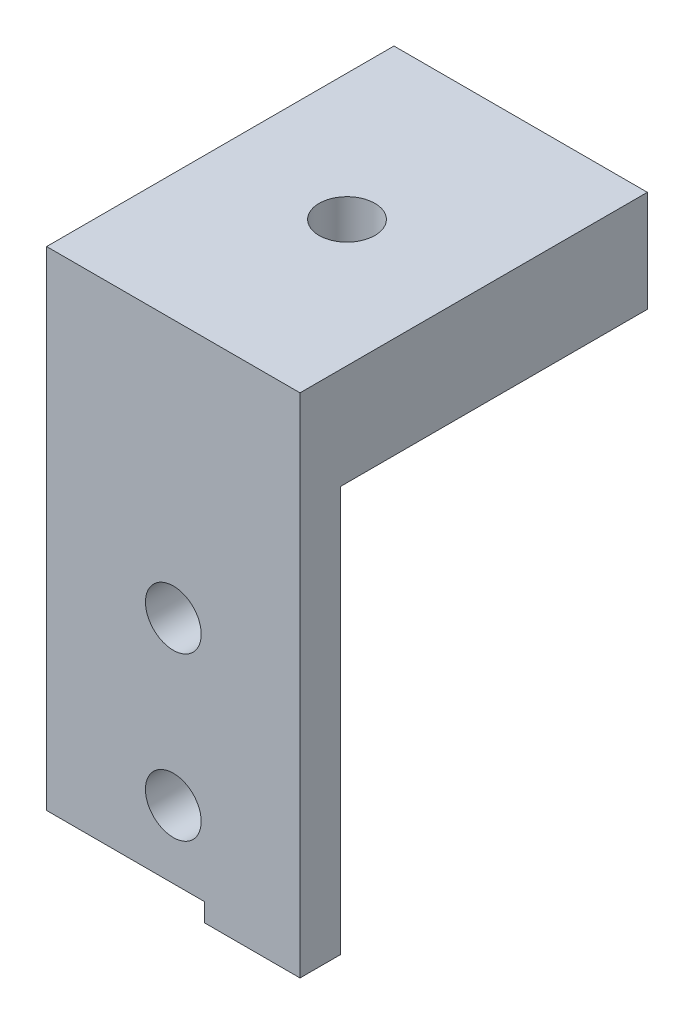
SolidWorks part; units mm, degrees
ref_plane "Front" through (0, 0, 0) normal (0, 0, 1) x (1, 0, 0)
ref_plane "Top" through (0, 0, 0) normal (0, 1, 0) x (1, 0, 0)
ref_plane "Right" through (0, 0, 0) normal (1, 0, 0) x (0, 0, -1)
sketch "Sketch1" plane through (0, 0, 0) normal (0, 1, 0) x (1, 0, 0)
  line L1 (0, 0) -> (12.5, 0)
  line L2 (0, 0) -> (0, 17.135)
  line L3 (0, 17.135) -> (12.5, 17.135)
  line L4 (12.5, 0) -> (12.5, 17.135)
  dimension "D1" = 12.5
  dimension "D2" = 17.135
extrude "tabBase" add sketch "Sketch1" along normal blind 5
sketch "Sketch2" plane through (0, 5, 0) normal (0, 1, 0) x (1, 0, 0)
  line L0 (0, 0) -> (12.5, 0) construction
  line L1 (0, 17.135) -> (0, 0) construction
  circle A0 centre (6.25, 8.5675) radius 1.375
  dimension "D1" = 2.75
  dimension "D2" = 8.5675
  dimension "D3" = 6.25
extrude "chassisMountingHole" cut sketch "Sketch2" against normal blind 5
sketch "Sketch3" plane through (0, 0, 0) normal (0, 0, 1) x (1, 0, 0)
  line L0 (12.5, 5) -> (12.5, 0) construction
  line L1 (0, 5) -> (12.5, 5)
  line L2 (0, 5) -> (0, -21)
  line L3 (0, -21) -> (12.5, -21)
  line L4 (12.5, 5) -> (12.5, -21)
  line L5 (12.5, 0) -> (0, 0) construction
  dimension "D1" = 21
extrude "frontTab" add sketch "Sketch3" against normal blind 5
sketch "frontMountingHolesSketch" plane through (0, 0, -5) normal (0, 0, -1) x (-1, 0, 0)
  line L0 (-12.5, -21) -> (-12.5, 0) construction
  line L1 (0, -21) -> (-12.5, -21) construction
  line L2 (-12.5, -10.5) -> (0, -10.5) construction
  line L3 (0, 0) -> (0, -21) construction
  circle A1 centre (-6.25, -15.75) radius 1.375
  circle A2 centre (-6.25, -7.75) radius 1.375
  point P5 (-6.25, -10.5)
  dimension "D1" = 2.75
  dimension "D2" = 5.25
  dimension "D3" = 8
extrude "frontMountingHoles" cut sketch "frontMountingHolesSketch" against normal blind 5
sketch "Sketch4" plane through (0, 0, -5) normal (0, 0, -1) x (-1, 0, 0)
  line L4 (0, 0) -> (-12.5, 0)
  line L5 (-12.5, 0) -> (-12.5, -21)
  line L6 (-12.5, -21) -> (0, -21)
  line L7 (0, -21) -> (0, 0)
  line L8 (0, 0) -> (-12.5, 0)
  line L9 (-12.5, 0) -> (-12.5, -21)
  line L10 (-12.5, -21) -> (0, -21)
  line L11 (0, -21) -> (0, 0)
  circle A0 centre (-6.25, -15.75) radius 1.375 construction
  circle A2 centre (-6.25, -15.75) radius 1.375
  circle A7 centre (-6.25, -7.75) radius 1.375
  dimension "D1" = 0
extrude "Cut-Extrude1" cut sketch "Sketch4" against normal offset from surface (3 mm away) 2 up to face at (7.625, -15.75, 0)
sketch "Sketch6" plane through (0, 0, -2) normal (0, 0, -1) x (-1, 0, 0)
  line L0 (0, 0) -> (0, -21) construction
  line L1 (-12.5, -21) -> (-4.7105, -21)
  line L2 (-12.5, -21) -> (-12.5, -19.094)
  line L3 (-12.5, -19.094) -> (-4.7105, -19.094)
  line L4 (-4.7105, -21) -> (-4.7105, -19.094)
  dimension "D1" = 4.7105
  dimension "D2" = 1.906
extrude "Cut-Extrude2" cut sketch "Sketch6" against normal blind 10
sketch "Sketch7" plane through (0, 0, -2) normal (0, 0, -1) x (-1, 0, 0)
  line L0 (-4.7105, -21) -> (-4.7105, -19.094) construction
  line L1 (0, -21) -> (-4.7105, -21)
  line L2 (0, -21) -> (0, -20)
  line L3 (0, -20) -> (-4.7105, -20)
  line L4 (-4.7105, -21) -> (-4.7105, -20)
  dimension "D1" = 1
extrude "Cut-Extrude3" cut sketch "Sketch7" against normal blind 10
mirror "Mirror1" about plane through (0, 5, 0) normal (1, 0, 0) of bodies 108
sketch "Sketch8" plane through (0, 0, -17.135) normal (0, 0, -1) x (-1, 0, 0)
  line L0 (-12.5, 5) -> (12.5, 5) construction
  line L1 (0, 5) -> (-19.6005, 5)
  line L2 (0, 5) -> (0, -25.4073)
  line L3 (0, -25.4073) -> (-19.6005, -25.4073)
  line L4 (-19.6005, 5) -> (-19.6005, -25.4073)
extrude "Cut-Extrude4" cut sketch "Sketch8" against normal through all both and the other way through all
